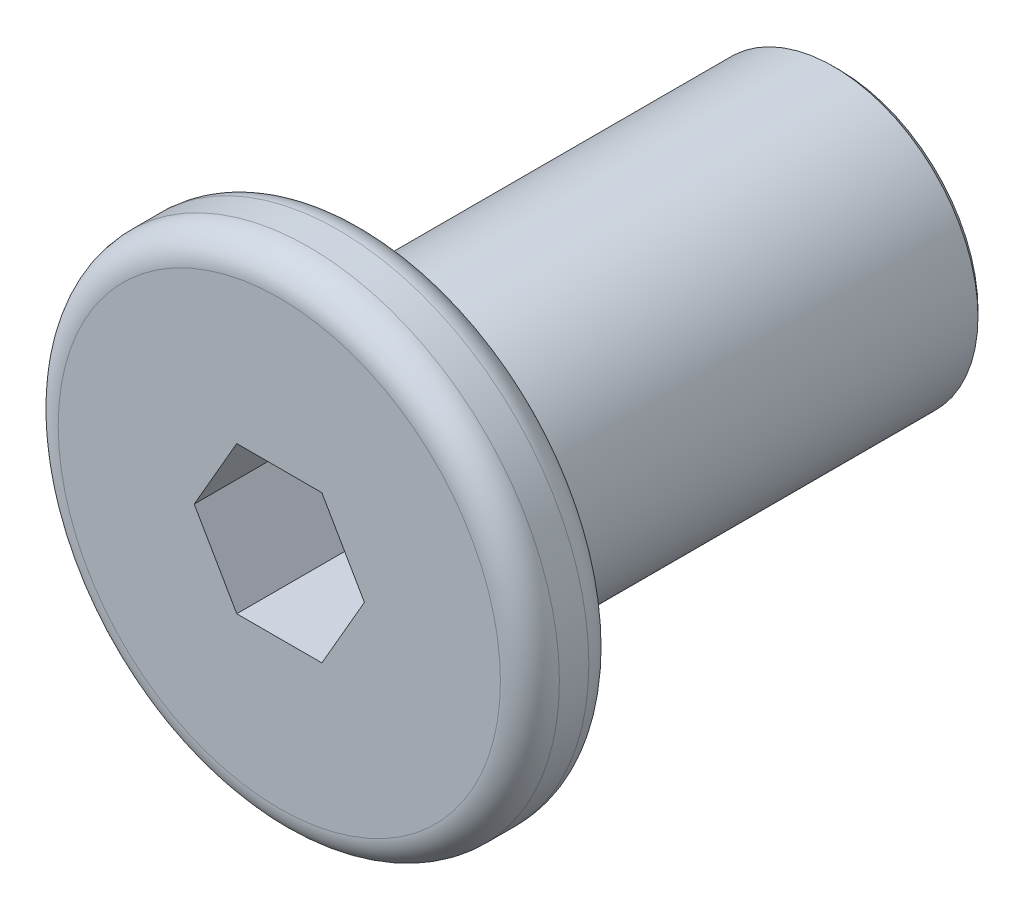
SolidWorks part; units mm, degrees
material "Простая углеродистая сталь"
ref_plane "Спереди" through (0, 0, 0) normal (0, 0, 1) x (1, 0, 0)
ref_plane "Сверху" through (0, 0, 0) normal (0, 1, 0) x (1, 0, 0)
ref_plane "Справа" through (0, 0, 0) normal (1, 0, 0) x (0, 0, -1)
sketch "Эскиз1" plane through (0, 0, 0) normal (0, 0, 1) x (1, 0, 0)
  circle A0 centre (0, 0) radius 4.25
  dimension "D1" = 8.5
extrude "Бобышка-Вытянуть1" add sketch "Эскиз1" along normal blind 1.5
sketch "Эскиз2" plane through (0, 0, 0) normal (0, 0, -1) x (-1, 0, 0)
  circle A0 centre (0, 0) radius 2.45
  dimension "D1" = 4.9
extrude "Бобышка-Вытянуть2" add sketch "Эскиз2" along normal blind 8
fillet "Скругление1" radius 0.5 2 edges at (4.25, 0, 1.5) (4.25, 0, 0)
sketch "Эскиз3" plane through (0, 0, 1.5) normal (0, 0, 1) x (1, 0, 0)
  line L1 (1.4434, 0) -> (0.7217, 1.25)
  line L2 (0.7217, 1.25) -> (-0.7217, 1.25)
  line L3 (-0.7217, 1.25) -> (-1.4434, 0)
  line L4 (-1.4434, 0) -> (-0.7217, -1.25)
  line L5 (-0.7217, -1.25) -> (0.7217, -1.25)
  line L6 (0.7217, -1.25) -> (1.4434, 0)
  circle A0 centre (0, 0) radius 1.25 construction
  dimension "D1" = 2.5
extrude "Вырез-Вытянуть1" cut sketch "Эскиз3" against normal blind 2
sketch "Skizze2" plane through (0, 0, -8) normal (0, 0, -1) x (-1, 0, 0)
  circle A0 centre (0, 0) radius 1.65
  dimension "D1" = 3.3
extrude "Schnitt-Linear austragen1" cut sketch "Skizze2" against normal offset from surface (7 mm away) 1 up to face at (3.75, 0, 0)
thread "Gewinde2" pitch 0.7 method cut profile "Gewindeprofil2" start angle 0, offset 1, length 0, pitch 0.7, diameter 3.3
ref_plane "Ebene2" through (1.65, 0, -9) normal (0, -1, 0) x (1, 0, 0)
sketch "Gewindeprofil2" plane through (1.65, 0, -9) normal (0, -1, 0) x (1, 0, 0)
  line L0 (0, 0) -> (0, 0.7) construction
  line L1 (0, 0) -> (0.3789, 0.2187)
  line L2 (0.3789, 0.2187) -> (0.3789, 0.3062)
  line L3 (0.3789, 0.3062) -> (0, 0.525)
  line L4 (0.3789, 0.2625) -> (0, 0.2625) construction
  line L11 (0, 0) -> (0, 0.525)
  point P2 (0, 0)
  dimension "Pitch" = 0.7
  dimension "Profile_Angle" = 60
  dimension "Profile_Land" = 0.0875
  dimension "Profile_Height" = 0.3789
sketch "Skizze7" plane through (0, 0, 0) normal (0, 1, 0) x (1, 0, 0)
  line L0 (0, 8) -> (2.1, 8)
  line L1 (2.45, 8) -> (-2.45, 8) construction
  line L2 (0, 8) -> (0, 24.3824) construction
  line L4 (1.5236, 8) -> (-1.4842, 8) construction
  line L5 (2.1, 8) -> (1.6, 7.5)
  line L6 (1.6, 7.5) -> (0, 7.5)
  line L7 (0, 7.5) -> (0, 8)
  point P12 (1.5138, 7.4505)
  dimension "D1" = 2.1
  dimension "D2" = 45
  dimension "D3" = 0.5
revolve "Schnitt-Rotation2" cut sketch "Skizze7" angle 360 about L7
chamfer "Fase2" distance 0.1 angle 45 1 edges at (-2.45, 0, -8)
